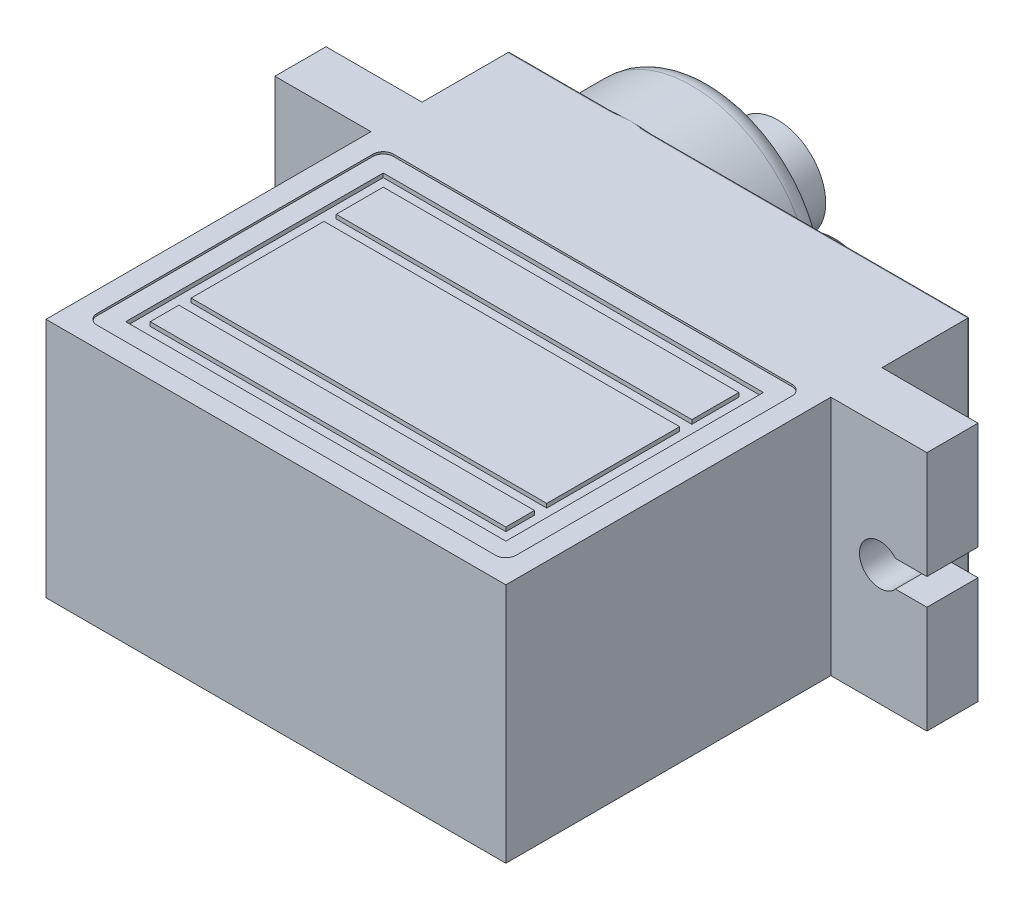
SolidWorks part; units mm, degrees
ref_plane "Front Plane" through (0, 0, 0) normal (0, 0, 1) x (1, 0, 0)
ref_plane "Top Plane" through (0, 0, 0) normal (0, 1, 0) x (1, 0, 0)
ref_plane "Right Plane" through (0, 0, 0) normal (1, 0, 0) x (0, 0, -1)
sketch "Sketch1" plane through (0, 0, 0) normal (0, 1, 0) x (1, 0, 0)
  line L1 (-11.25, -11.35) -> (11.25, -11.35)
  line L2 (-11.25, -11.35) -> (-11.25, 11.35)
  line L3 (-11.25, 11.35) -> (11.25, 11.35)
  line L4 (11.25, -11.35) -> (11.25, 11.35)
  line L5 (-11.25, -11.35) -> (11.25, 11.35) construction
  line L6 (-11.25, 11.35) -> (11.25, -11.35) construction
  point P0 (0, 0)
  dimension "D1" = 22.5
  dimension "D2" = 22.7
extrude "Boss-Extrude1" add sketch "Sketch1" along normal mid plane 11.8
sketch "Sketch2" plane through (11.25, 0, 0) normal (1, 0, 0) x (0, 0, -1)
  line L0 (-11.35, -5.9) -> (11.35, -5.9) construction
  line L1 (7.05, -5.9) -> (4.55, -5.9)
  line L2 (7.05, -5.9) -> (7.05, 5.9)
  line L3 (7.05, 5.9) -> (4.55, 5.9)
  line L4 (4.55, -5.9) -> (4.55, 5.9)
  line L5 (-11.35, 5.9) -> (11.35, 5.9) construction
  line L6 (-11.35, 5.9) -> (-11.35, -5.9) construction
  dimension "D1" = 2.5
  dimension "D2" = 15.9
extrude "Boss-Extrude2" add sketch "Sketch2" along normal blind 4.7
sketch "Sketch3" plane through (-11.25, 0, 0) normal (-1, 0, 0) x (0, 0, 1)
  line L0 (-11.35, -5.9) -> (11.35, -5.9) construction
  line L1 (-7.05, -5.9) -> (-4.55, -5.9)
  line L2 (-7.05, -5.9) -> (-7.05, 5.9)
  line L3 (-7.05, 5.9) -> (-4.55, 5.9)
  line L4 (-4.55, -5.9) -> (-4.55, 5.9)
  line L5 (-11.35, 5.9) -> (11.35, 5.9) construction
  line L6 (11.35, 5.9) -> (11.35, -5.9) construction
  dimension "D1" = 15.9
  dimension "D2" = 2.5
extrude "Boss-Extrude3" add sketch "Sketch3" along normal blind 4.7
sketch "Sketch4" plane through (0, 0, -11.35) normal (0, 0, -1) x (-1, 0, 0)
  line L0 (11.25, 5.9) -> (11.25, -5.9) construction
  line L1 (-11.25, -5.9) -> (11.25, -5.9) construction
  arc A0 (-0.0667, -2.3387) -> (-0.0667, 2.3387) centre (5.35, 0) ccw
  arc A1 (-0.0667, 2.3387) -> (-0.0667, -2.3387) centre (-0.95, 0) ccw
  dimension "D1" = 11.8
  dimension "D4" = 5
  dimension "D2" = 5.9
  dimension "D3" = 5.9
  dimension "D5" = 6.3
extrude "Boss-Extrude5" add sketch "Sketch4" along normal blind 4
sketch "Sketch7" plane through (0, 0, -7.05) normal (0, 0, -1) x (-1, 0, 0)
  line L0 (-15.95, -5.9) -> (-15.95, 5.9) construction
  line L1 (-14.4099, 0.65) -> (-15.95, 0.65)
  line L2 (-15.95, 0.65) -> (-15.95, -0.65)
  line L3 (-15.95, -0.65) -> (-14.4099, -0.65)
  line L4 (14.4099, 0.65) -> (15.95, 0.65)
  line L5 (15.95, 5.9) -> (15.95, -5.9) construction
  line L6 (15.95, 0.65) -> (15.95, -0.65)
  line L7 (15.95, -0.65) -> (14.4099, -0.65)
  line L10 (-15.95, 5.9) -> (-11.25, 5.9) construction
  line L11 (15.95, 5.9) -> (11.25, 5.9) construction
  line L12 (12.1344, 0) -> (15.1656, 0) construction
  line L13 (-12.15, 0) -> (-15.15, 0) construction
  arc A0 (-14.4099, -0.65) -> (-14.4099, 0.65) centre (-13.65, 0) ccw
  arc A1 (14.4099, 0.65) -> (14.4099, -0.65) centre (13.65, 0) ccw
  dimension "D3" = 2
  dimension "D4" = 2
  dimension "D1" = 5.9
  dimension "D2" = 5.9
  dimension "D5" = 2.3
  dimension "D6" = 2.3
  dimension "D7" = 0.65
  dimension "D8" = 0.65
  dimension "D9" = 3
  dimension "D10" = 0.65
  dimension "D11" = 0.65
extrude "Cut-Extrude6" cut sketch "Sketch7" against normal through all
sketch "Sketch11" plane through (0, 5.9, 0) normal (0, 1, 0) x (1, 0, 0)
  line L1 (-9.75, -10.35) -> (9.75, -10.35)
  line L2 (-10.25, -9.85) -> (-10.25, 3.65)
  line L3 (-9.75, 4.15) -> (9.75, 4.15)
  line L4 (10.25, -9.85) -> (10.25, 3.65)
  line L5 (-10.25, -10.35) -> (10.25, 4.15) construction
  line L6 (-10.25, 4.15) -> (10.25, -10.35) construction
  line L7 (-11.25, -11.35) -> (11.25, -11.35) construction
  line L8 (11.25, -11.35) -> (11.25, 4.55) construction
  line L9 (-11.25, 4.55) -> (-11.25, -11.35) construction
  arc A0 (-9.75, -10.35) -> (-10.25, -9.85) centre (-9.75, -9.85) cw
  arc A1 (9.75, -10.35) -> (10.25, -9.85) centre (9.75, -9.85) ccw
  arc A2 (9.75, 4.15) -> (10.25, 3.65) centre (9.75, 3.65) cw
  arc A3 (-10.25, 3.65) -> (-9.75, 4.15) centre (-9.75, 3.65) cw
  point P0 (0, -3.1)
  dimension "D1" = 0.5
  dimension "D2" = 13.5
  dimension "D3" = 1
  dimension "D4" = 1
  dimension "D5" = 1
extrude "Cut-Extrude7" cut sketch "Sketch11" against normal blind 0.1
fillet "Fillet8" radius 0.1 7 edges at (-11.25, 2.95, -11.35) (-11.25, -2.95, -11.35) (-8.3, -5.9, -11.35) (11.25, 0, -11.35) (2.95, -5.9, -11.35) (2.95, 5.9, -11.35) (-8.3, 5.9, -11.35)
sketch "Sketch18" plane through (0, 5.8, 0) normal (0, 1, 0) x (1, 0, 0)
  line L0 (-8.7, 0.3) -> (-8.7, 2.6)
  line L1 (8.7, -0.3) -> (8.7, -6.8)
  line L2 (8.7, -7.4) -> (8.7, -8.8)
  line L3 (-8.7, -6.8) -> (-8.7, -0.3)
  line L5 (9.75, 4.15) -> (-9.75, 4.15) construction
  line L6 (-10.25, 3.65) -> (-10.25, -9.85) construction
  line L7 (10.25, -9.85) -> (10.25, 3.65) construction
  line L10 (-9.3, 3.2) -> (9.3, 3.2)
  line L11 (9.3, 3.2) -> (9.3, -9.4)
  line L12 (9.3, -9.4) -> (-9.3, -9.4)
  line L13 (-9.3, -9.4) -> (-9.3, 3.2)
  line L14 (-8.7, -0.3) -> (8.7, -0.3)
  line L15 (-8.7, -7.4) -> (8.7, -7.4)
  line L16 (-8.7, 2.6) -> (8.7, 2.6)
  line L17 (8.7, 2.6) -> (8.7, 0.3)
  line L18 (8.7, -8.8) -> (-8.7, -8.8)
  line L19 (-8.7, -8.8) -> (-8.7, -7.4)
  line L20 (-8.7, 0.3) -> (8.7, 0.3)
  line L21 (-8.7, -6.8) -> (8.7, -6.8)
  dimension "D1" = 12.6
  dimension "D2" = 17.4
  dimension "D3" = 17.4
  dimension "D4" = 17.4
  dimension "D5" = 18.6
  dimension "D6" = 17.4
  dimension "D7" = 17.4
  dimension "D8" = 17.4
  dimension "D9" = 1.4
  dimension "D10" = 0.95
  dimension "D11" = 0.6
  dimension "D12" = 0.6
  dimension "D13" = 0.95
  dimension "D14" = 0.95
  dimension "D15" = 0.6
  dimension "D16" = 0.6
extrude "Cut-Extrude16" cut sketch "Sketch18" against normal blind 0.2
fillet "Fillet9" radius 1 2 edges at (3.45, 0, -15.35) (-11.25, 0, -15.35)
sketch "Sketch20" plane through (0, 0, -15.35) normal (0, 0, -1) x (-1, 0, 0)
  circle A0 centre (5.35, 0) radius 2.35
  dimension "D1" = 4.7
extrude "Boss-Extrude6" add sketch "Sketch20" along normal blind 3.2
sketch "Sketch21" plane through (0, 0, -18.55) normal (0, 0, -1) x (-1, 0, 0)
  circle A0 centre (5.35, 0) radius 1
  dimension "D1" = 2
extrude "Cut-Extrude18" cut sketch "Sketch21" against normal blind 0.225
sketch "Sketch23" plane through (0, 0, -18.325) normal (0, 0, -1) x (-1, 0, 0)
  line L0 (5.35, -0.82) -> (5.35, 0.82) construction
  line L1 (5.17, -0.82) -> (5.17, -0.18)
  line L2 (5.53, -0.82) -> (5.53, -0.18)
  line L3 (6.17, 0) -> (4.53, 0) construction
  line L4 (6.17, -0.18) -> (5.53, -0.18)
  line L5 (6.17, 0.18) -> (5.53, 0.18)
  line L6 (5.17, 0.18) -> (4.53, 0.18)
  line L7 (5.53, 0.18) -> (5.53, 0.82)
  line L8 (5.17, -0.18) -> (4.53, -0.18)
  line L9 (5.17, 0.18) -> (5.17, 0.82)
  arc A0 (5.17, -0.82) -> (5.53, -0.82) centre (5.35, -0.82) ccw
  arc A1 (5.53, 0.82) -> (5.17, 0.82) centre (5.35, 0.82) ccw
  arc A2 (6.17, -0.18) -> (6.17, 0.18) centre (6.17, 0) ccw
  arc A3 (4.53, 0.18) -> (4.53, -0.18) centre (4.53, 0) ccw
  circle A4 centre (5.35, 0) radius 1 construction
  point P2 (5.35, 0)
  point P9 (5.35, 0)
  dimension "D1" = 0.18
  dimension "D2" = 0.18
  dimension "D3" = 0.18
  dimension "D4" = 0.18
  dimension "D5" = 0.64
  dimension "D6" = 0.64
  dimension "D7" = 0.64
  dimension "D8" = 0.64
  dimension "D9" = 0.64
  dimension "D10" = 0.64
  dimension "D11" = 0.64
  dimension "D12" = 0.36
extrude "Cut-Extrude19" cut sketch "Sketch23" against normal blind 1
